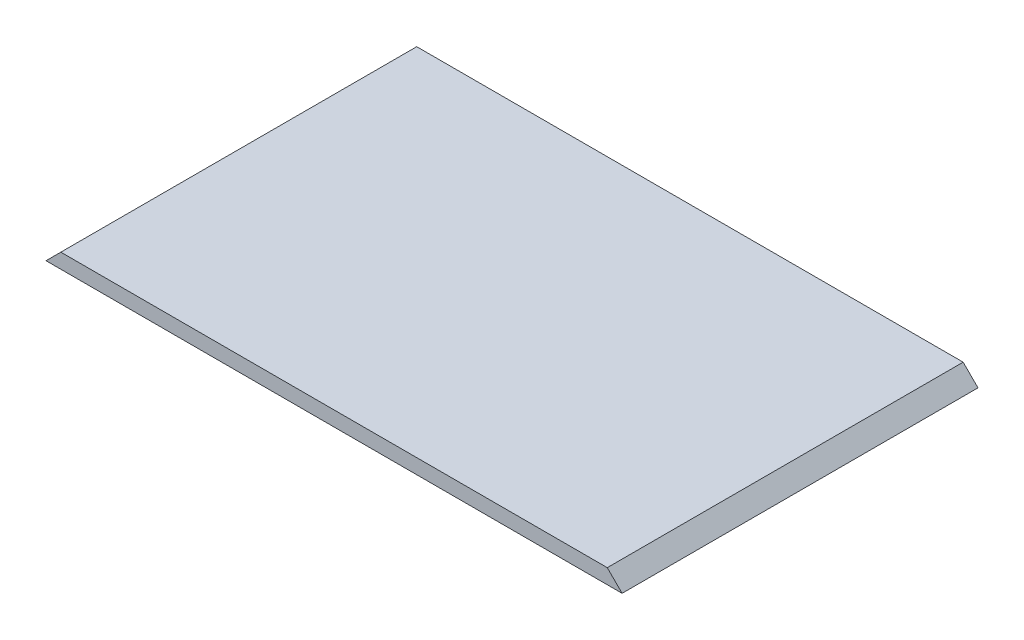
SolidWorks part; units mm, degrees
ref_plane "Front Plane" through (0, 0, 0) normal (0, 0, 1) x (1, 0, 0)
ref_plane "Top Plane" through (0, 0, 0) normal (0, 1, 0) x (1, 0, 0)
ref_plane "Right Plane" through (0, 0, 0) normal (1, 0, 0) x (0, 0, -1)
sketch "Sketch2" plane through (0, 0, 0) normal (0, 1, 0) x (1, 0, 0)
  line L0 (-249.6269, 0) -> (249.6269, 0) construction
  line L1 (0, -111.6046) -> (0, 111.6046) construction
  line L3 (-127, -76.2) -> (127, -76.2)
  line L4 (-127, -76.2) -> (-127, 76.2)
  line L5 (-127, 76.2) -> (127, 76.2)
  line L6 (127, -76.2) -> (127, 76.2)
  line L7 (0, 76.2) -> (0, -76.2) construction
  line L8 (-127, 0) -> (127, 0) construction
  point P0 (0, 0)
  point P4 (0, 0)
  point P8 (0, 0)
  dimension "D1" = 152.4
  dimension "D2" = 254
extrude "Boss-Extrude1" add sketch "Sketch2" along normal mid plane 6.35 contours L4 L3 L6 L5
chamfer "Chamfer1" distance 10 angle 45 1 edges at (-127, 3.175, 0)
chamfer "Chamfer2" distance 10 angle 45 1 edges at (127, 3.175, 0)
